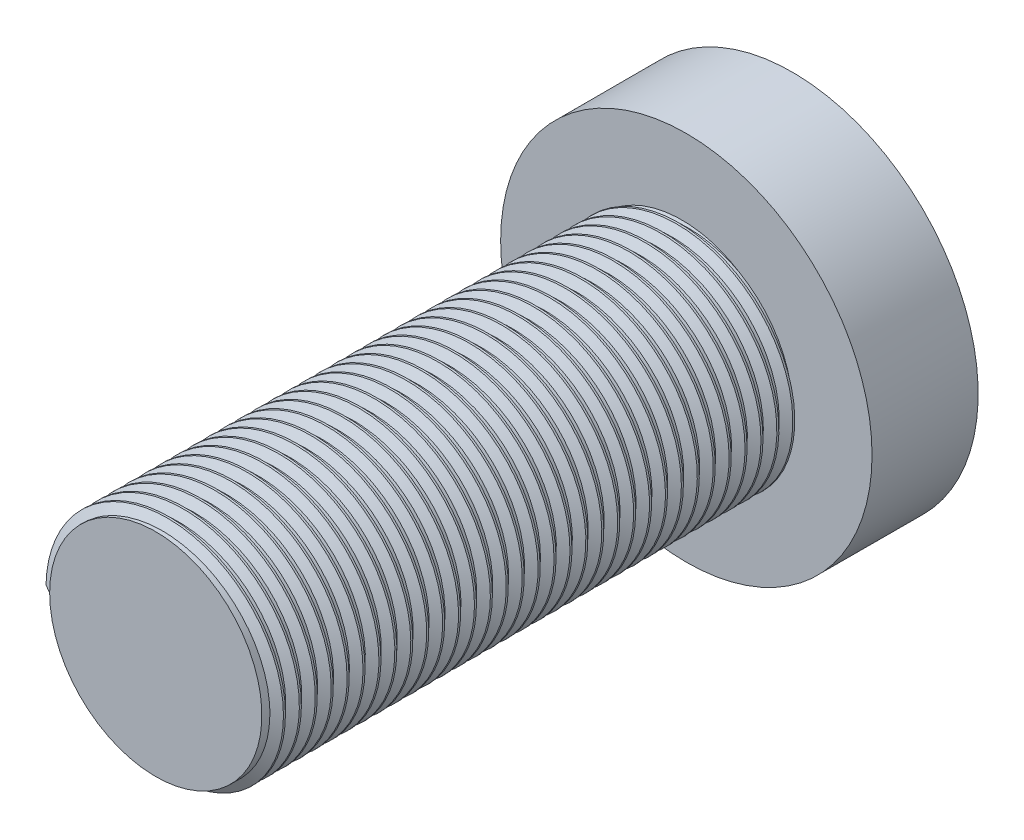
SolidWorks part; units mm, degrees
ref_plane "前视基准面" through (0, 0, 0) normal (0, 0, 1) x (1, 0, 0)
ref_plane "上视基准面" through (0, 0, 0) normal (0, 1, 0) x (1, 0, 0)
ref_plane "右视基准面" through (0, 0, 0) normal (1, 0, 0) x (0, 0, -1)
sketch "草图1" plane through (0, 0, 0) normal (0, 0, 1) x (1, 0, 0)
  circle A0 centre (0, 0) radius 3.5
  dimension "D1" = 7
extrude "凸台-拉伸1" add sketch "草图1" along normal blind 1
sketch "草图2" plane through (0, 0, 1) normal (0, 0, 1) x (1, 0, 0)
  circle A0 centre (0, 0) radius 2
  dimension "D1" = 4
extrude "凸台-拉伸2" add sketch "草图2" along normal blind 10
sketch "草图3" plane through (0, 0, 0) normal (0, 0, -1) x (-1, 0, 0)
  circle A0 centre (0, 0) radius 3.5
extrude "凸台-拉伸3" add sketch "草图3" along normal blind 1
thread "螺纹线1" pitch 0.3 method extrude profile "螺纹线轮廓1" start angle 0, offset 0, length 10, pitch 0.3, diameter 4
ref_plane "基准面1" through (-2, 0, 11) normal (0, -1, 0) x (-1, 0, 0)
sketch "螺纹线轮廓1" plane through (-2, 0, 11) normal (0, -1, 0) x (-1, 0, 0)
  line L0 (0, 0) -> (0, 0.3) construction
  line L1 (0, 0) -> (0.1624, 0.0937)
  line L2 (0.1624, 0.0937) -> (0.1624, 0.1312)
  line L3 (0.1624, 0.1312) -> (0, 0.225)
  line L4 (0.1624, 0.1125) -> (0, 0.1125) construction
  line L11 (0, 0) -> (0, 0.225)
  point P2 (0, 0)
  dimension "Pitch" = 0.3
  dimension "Profile_Angle" = 60
  dimension "Profile_Land" = 0.0375
  dimension "Profile_Height" = 0.1624
sketch "草图8" plane through (0, 0, -1) normal (0, 0, -1) x (-1, 0, 0)
  line L1 (-0.5, 2.25) -> (0.5, 2.25)
  line L2 (-0.5, 2.25) -> (-0.5, -2.25)
  line L3 (-0.5, -2.25) -> (0.5, -2.25)
  line L4 (0.5, 2.25) -> (0.5, -2.25)
  line L5 (-0.5, 2.25) -> (0.5, -2.25) construction
  line L6 (-0.5, -2.25) -> (0.5, 2.25) construction
  point P0 (0, 0)
  dimension "D1" = 4.5
  dimension "D2" = 1
extrude "切除-拉伸1" cut sketch "草图8" against normal blind 0.5
sketch "草图9" plane through (0, 0, -1) normal (0, 0, -1) x (-1, 0, 0)
  line L1 (-2.3067, 0.3488) -> (2.3067, 0.3488)
  line L2 (-2.3067, 0.3488) -> (-2.3067, -0.3488)
  line L3 (-2.3067, -0.3488) -> (2.3067, -0.3488)
  line L4 (2.3067, 0.3488) -> (2.3067, -0.3488)
  line L5 (-2.3067, 0.3488) -> (2.3067, -0.3488) construction
  line L6 (-2.3067, -0.3488) -> (2.3067, 0.3488) construction
  point P0 (0, 0)
